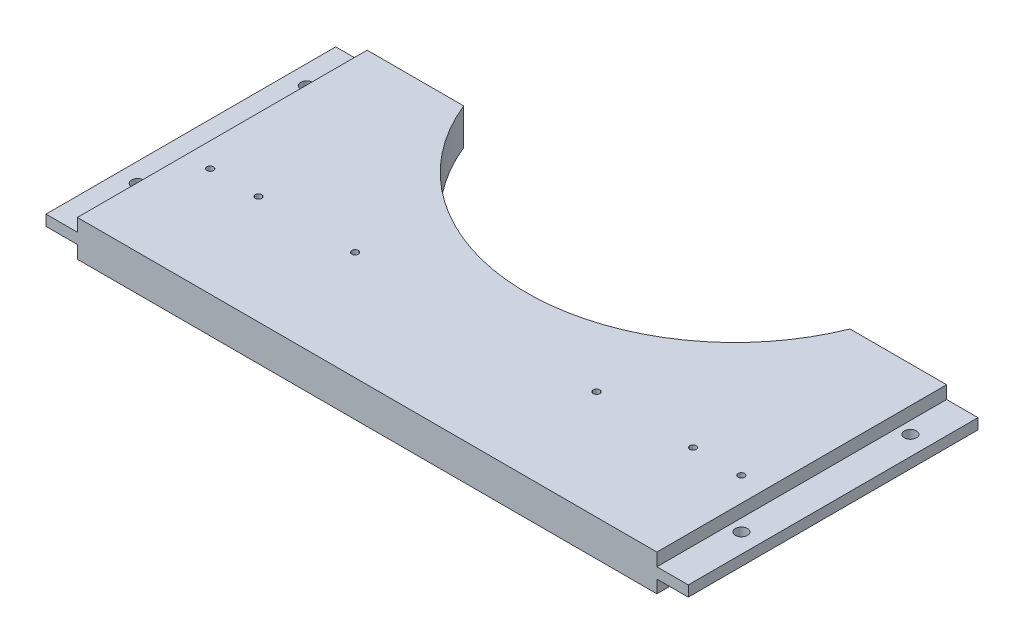
SolidWorks part; units mm, degrees
ref_plane "Front" through (0, 0, 0) normal (0, 0, 1) x (1, 0, 0)
ref_plane "Top" through (0, 0, 0) normal (0, 1, 0) x (1, 0, 0)
ref_plane "Right" through (0, 0, 0) normal (1, 0, 0) x (0, 0, -1)
sketch "Sketch1" plane through (0, 0, 0) normal (0, 1, 0) x (1, 0, 0)
  line L0 (-101.6, 76.2) -> (-152.4, 76.2)
  line L5 (-152.4, 76.2) -> (-152.4, -76.2)
  line L6 (-152.4, -76.2) -> (152.4, -76.2)
  line L7 (152.4, -76.2) -> (152.4, 76.2)
  line L8 (152.4, 76.2) -> (101.6, 76.2)
  line L9 (0, -50) -> (0, 50) construction
  line L10 (-24.4982, 7.62) -> (79.6476, 7.62) construction
  line L11 (-50, 0) -> (50, 0) construction
  circle A0 centre (0, 117.1693) radius 109.5493
  point P5 (152.4, 0)
  point P11 (0, -76.2)
  dimension "D1" = 152.4
  dimension "D2" = 83.82
  dimension "D3" = 50.8
  dimension "D4" = 304.8
extrude "Boss-Extrude1" add sketch "Sketch1" along normal mid plane 19.05 contours L5 L10 A0 L0 | L10 L5 L6 L7 | A0 L10 L7 L8 region at (0, 0, 13.2803)
sketch "Sketch2" plane through (0, 9.525, 0) normal (0, 1, 0) x (1, 0, 0)
  line L0 (-152.4, -19.05) -> (152.4, -19.05) construction
  line L1 (-152.4, 76.2) -> (-152.4, -76.2) construction
  line L2 (152.4, -76.2) -> (152.4, 76.2) construction
  line L3 (-152.4, -76.2) -> (152.4, -76.2) construction
  point P8 (-139.7, -19.05)
  point P9 (-114.3, -19.05)
  point P10 (-63.5, -19.05)
  dimension "D1" = 57.15
  dimension "D2" = 12.7
  dimension "D3" = 25.4
  dimension "D4" = 50.8
hole_wizard "#8-32 Tapped Hole1" positions "Sketch3" profile "Sketch5" tap size "#8-32" standard "ANSI Inch" end condition through all
sketch "Sketch3" plane through (0, 9.525, 0) normal (0, 1, 0) x (1, 0, 0)
  point P0 (-139.7, -19.05)
  point P3 (-114.3, -19.05)
  point P6 (-63.5, -19.05)
sketch "Sketch5" plane through (-139.7, 9.525, 19.05) normal (1, 0, 0) x (0, 0, 1)
  line L0 (0, 0) -> (0, 19.05)
  line L1 (0, 19.05) -> (1.7272, 19.05)
  line L2 (1.7272, 19.05) -> (1.7272, 0)
  line L5 (1.7272, 0) -> (0, 0)
  line L11 (0, -6.35) -> (0, 107.95) construction
  dimension "Thru Tap Drill Dia." = 3.4544
  dimension "Thru Tap Drill Depth" = 19.05
cosmetic thread "Hole Thread1" parameters "D2"=4.1656
cosmetic thread "Hole Thread2" parameters "D2"=4.1656
cosmetic thread "Hole Thread3" parameters "D2"=4.1656
mirror "Mirror1" about plane through (0, 0, 0) normal (1, 0, 0) of "#8-32 Tapped Hole1"
cosmetic thread "Hole Thread4" parameters "D2"=4.1656
cosmetic thread "Hole Thread5" parameters "D2"=4.1656
cosmetic thread "Hole Thread6" parameters "D2"=4.1656
sketch "Sketch6" plane through (0, 0, 0) normal (0, 1, 0) x (1, 0, 0)
  line L0 (-152.4, -76.2) -> (152.4, -76.2) construction
  line L1 (-152.4, 76.2) -> (-168.91, 76.2)
  line L2 (-152.4, 76.2) -> (-152.4, -76.2)
  line L3 (-152.4, -76.2) -> (-168.91, -76.2)
  line L4 (-168.91, 76.2) -> (-168.91, -76.2)
  dimension "D1" = 16.51
extrude "Boss-Extrude2" add sketch "Sketch6" along normal mid plane 5.588
sketch "Sketch7" plane through (0, 2.794, 0) normal (0, 1, 0) x (1, 0, 0)
  line L1 (-152.4, 76.2) -> (-168.91, 76.2) construction
  line L2 (-168.91, -76.2) -> (-152.4, -76.2) construction
  line L3 (-152.4, 76.2) -> (-152.4, -76.2) construction
  point P0 (-158.75, 50.8)
  point P1 (-158.75, -38.1)
  point P2 (0, 0)
  point P8 (0, 0)
  dimension "D1" = 25.4
  dimension "D2" = 38.1
  dimension "D3" = 6.35
hole_wizard "1/4 (0.25) Diameter Hole1" positions "Sketch8" profile "Sketch10" hole size "1/4" standard "ANSI Inch" end condition through all
sketch "Sketch8" plane through (0, 2.794, 0) normal (0, 1, 0) x (1, 0, 0)
  point P0 (-158.75, 50.8)
  point P3 (-158.75, -38.1)
sketch "Sketch10" plane through (-158.75, 2.794, -50.8) normal (1, 0, 0) x (0, 0, 1)
  line L0 (0, 0) -> (0, 12.319)
  line L1 (0, 12.319) -> (3.175, 12.319)
  line L2 (3.175, 12.319) -> (3.175, 0)
  line L5 (3.175, 0) -> (0, 0)
  line L11 (0, -6.35) -> (0, 107.95) construction
  dimension "Thru Hole Dia." = 6.35
  dimension "Thru Hole Depth" = 12.319
mirror "Mirror2" about plane through (0, 0, 0) normal (1, 0, 0) of "1/4 (0.25) Diameter Hole1", "Boss-Extrude2"
